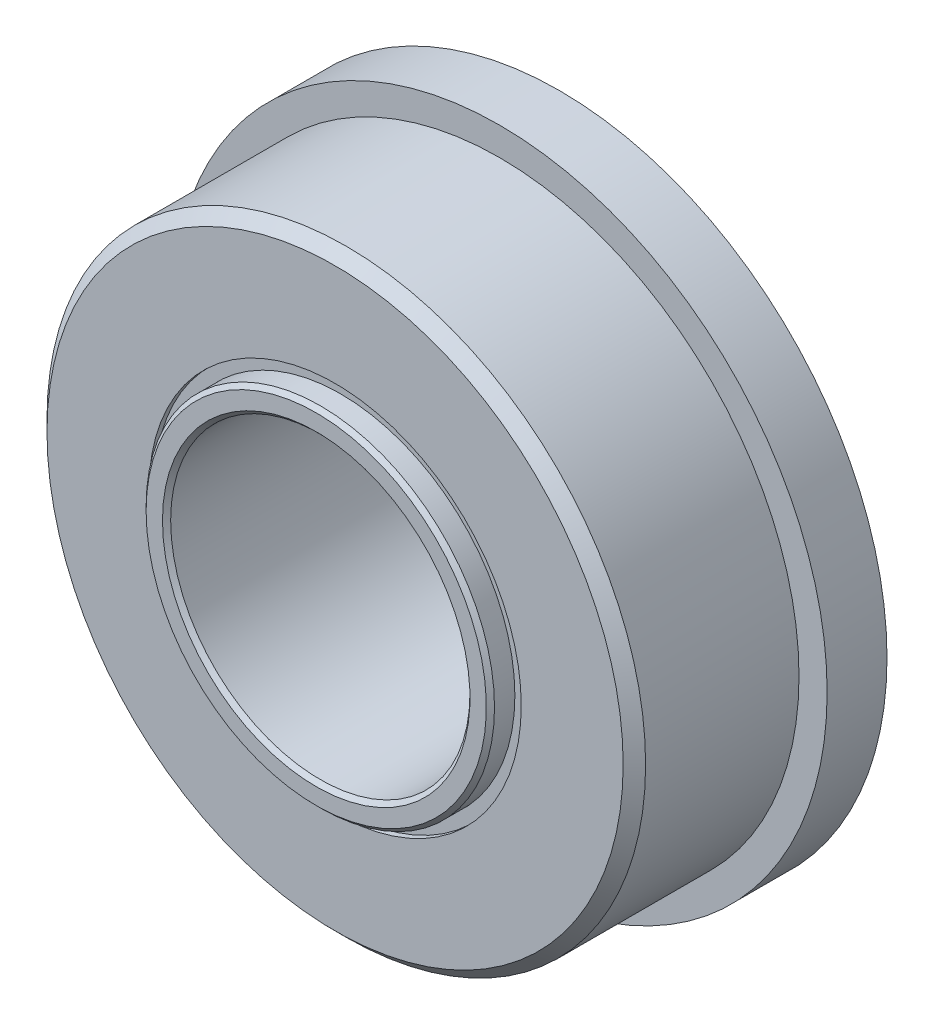
SolidWorks part; units mm, degrees
note: '?' marks a value the reader was unsure of.
ref_plane "Front Plane" through (0, 0, 0) normal (0, 0, 1) x (1, 0, 0)
ref_plane "Top Plane" through (0, 0, 0) normal (0, 1, 0) x (1, 0, 0)
ref_plane "Right Plane" through (0, 0, 0) normal (1, 0, 0) x (0, 0, -1)
sketch "Sketch1" plane through (0, 0, 0) normal (1, 0, 0) x (0, 0, -1)
  line L0 (-2.3813, 0) -> (2.3813, 0) construction
  line L1 (0, 6.35) -> (0, -6.35) construction
  line L2 (2.1431, 6.35) -> (-2.1431, 6.35)
  line L3 (-2.1431, 6.35) -> (-2.3812, 6.1119)
  line L4 (-2.3812, 6.1119) -> (-2.3812, 3.9497)
  line L5 (-2.3812, 3.9497) -> (-0.7429, 3.9497)
  line L6 (2.3813, 3.9497) -> (0.743, 3.9497)
  line L7 (2.3812, 6.1119) -> (2.3813, 3.9497)
  line L8 (2.1431, 6.35) -> (2.3812, 6.1119)
  line L9 (0, 6.35) -> (0, 4.7625) construction
  line L10 (0, 4.7625) -> (0, 3.175) construction
  line L11 (2.3813, 3.6957) -> (2.3813, -3.6957) construction
  line L12 (2.7813, 3.6957) -> (0.5878, 3.6957)
  line L13 (-2.7813, 3.6957) -> (-2.7813, 3.175)
  line L14 (-2.7813, 3.175) -> (2.7813, 3.175)
  line L15 (2.7813, 3.175) -> (2.7813, 3.6957)
  line L16 (-2.7813, 3.4353) -> (2.7813, 3.4354) construction
  line L17 (-0.5878, 3.6957) -> (-2.7813, 3.6957)
  circle A1 centre (0, 4.2291) radius 0.7938 construction
  arc A2 (-0.7429, 3.9497) -> (0.743, 3.9497) centre (0, 4.2291) cw
  arc A3 (-0.5878, 3.6957) -> (0.5878, 3.6957) centre (0, 4.2291) ccw
  point P14 (0, 3.175)
  dimension "D3" = 0.5207
  dimension "D4" = 1.5875
  dimension "D1" = 45
  dimension "Width" = 4.7625
  dimension "OD" = 12.7
  dimension "D2" = 0.2381
  dimension "Shaft Dia" = 6.35
  dimension "D5" = 0.254
  dimension "Inner Ring" = 7.3914
  dimension "Ring Width" = 5.5626
revolve "Revolve1" add sketch "Sketch1" angle 360 about L0
sketch "Sketch4" plane through (0, 0, 0) normal (1, 0, 0) x (0, 0, -1)
  line L0 (-0.7937, 4.2291) -> (0.7938, 4.2291)
  circle A0 centre (0, 4.2291) radius 0.7938 construction
  arc A2 (-0.7937, 4.2291) -> (0.7938, 4.2291) centre (0, 4.2291) cw
revolve "Revolve4" add sketch "Sketch4" angle 360 about L0
chamfer "Chamfer1" distance 0.0868 angle 45 4 edges at (3.6957, 0, 2.7813) (3.175, 0, 2.7813) (3.175, 0, -2.7813) (3.6957, 0, -2.7813)
ref_axis "Axis1" through (0, 0, -2.3813) along (0, 0, 1)?
pattern_circular "CirPattern1" count 12 every 30 about axis through (0, 0, 0) along (0, 0, 1) of bodies 104
sketch "Sketch5" plane through (0, 0, 0) normal (1, 0, 0) x (0, 0, -1)
  line L0 (-2.3812, 3.9497) -> (-0.7429, 3.9497) construction
  line L1 (-2.2622, 3.9497) -> (-0.7937, 3.9497)
  line L2 (-2.2622, 3.9497) -> (-2.2622, 3.6957)
  line L3 (-2.2622, 3.6957) -> (-0.7937, 3.6957)
  line L4 (-0.7937, 3.9497) -> (-0.7937, 3.6957)
  line L6 (2.3813, 3.9497) -> (0.743, 3.9497) construction
  line L7 (2.2622, 3.9497) -> (0.7938, 3.9497)
  line L8 (2.2622, 3.9497) -> (2.2622, 3.6957)
  line L9 (2.2622, 3.6957) -> (0.7938, 3.6957)
  line L10 (0.7938, 3.9497) -> (0.7938, 3.6957)
  line L12 (-2.1431, 6.35) -> (-2.3812, 6.1119) construction
  line L13 (-0.5878, 3.6957) -> (-2.7813, 3.6957) construction
  line L14 (2.7813, 3.6957) -> (0.5878, 3.6957) construction
  point P18 (-2.2622, 6.2309)
revolve "Revolve5" add sketch "Sketch5" angle 360 about L0
sketch "Sketch6" plane through (0, 0, 0) normal (1, 0, 0) x (0, 0, -1)
  line L1 (2.3813, 3.9497) -> (1.1113, 3.9497)
  line L2 (2.3813, 3.9497) -> (2.3813, 6.9469)
  line L3 (2.3813, 6.9469) -> (1.1113, 6.9469)
  line L4 (1.1113, 3.9497) -> (1.1113, 6.9469)
  line L5 (2.3813, 0) -> (-2.3813, 0) construction
  dimension "Flange OD" = 13.8938
  dimension "Th" = 1.27
revolve "Revolve6" add sketch "Sketch6" angle 360 about L5
equation "\"D2@Sketch1\" = \"Width@Sketch1\"*.05"
equation "\"D2@CirPattern1\" = 360/\"Balls@CirPattern1\""
equation "\"D4@Sketch1\"=\"Width@Sketch1\"/3"
equation "\"D1@Chamfer1\"=\"D3@Sketch1\"/6"
